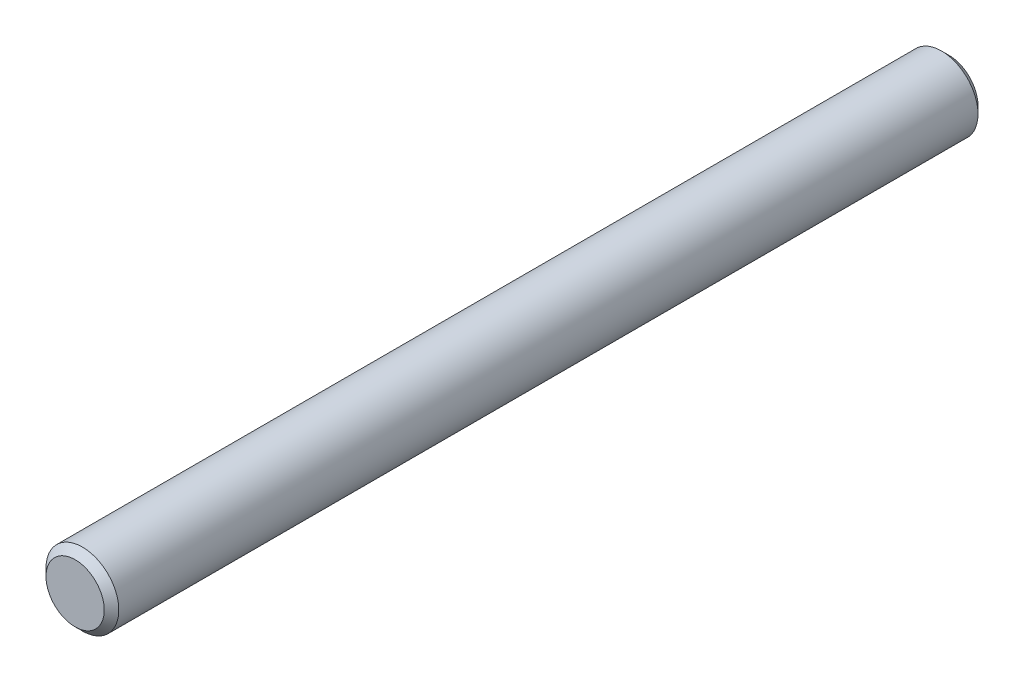
SolidWorks part; units mm, degrees
material "Plain Carbon Steel"
ref_plane "Front" through (0, 0, 0) normal (0, 0, 1) x (1, 0, 0)
ref_plane "Top" through (0, 0, 0) normal (0, 1, 0) x (1, 0, 0)
ref_plane "Right" through (0, 0, 0) normal (1, 0, 0) x (0, 0, -1)
sketch "Sketch1" plane through (0, 0, 0) normal (0, 0, 1) x (1, 0, 0)
  circle A0 centre (0, 0) radius 12.7
  dimension "dia" = 25.4
extrude "Extrude1" add sketch "Sketch1" along normal mid plane 304.8
sketch "Sketch2" plane through (0, 0, 0) normal (1, 0, 0) x (0, 0, -1)
  line L0 (152.4, 12.7) -> (148.59, 12.7) construction
  line L1 (152.4, 12.7) -> (-152.4, 12.7) construction
  line L2 (148.59, 12.7) -> (117.6337, 12.7) construction
  line L3 (117.6337, 12.7) -> (110.49, 12.7) construction
  line L4 (110.49, 12.7) -> (101.6, 12.7) construction
  line L5 (101.6, 12.7) -> (98.9432, 12.7) construction
  line L7 (90.0532, 12.7) -> (83.7032, 12.7) construction
  line L8 (83.7032, 12.7) -> (74.8132, 12.7) construction
  line L10 (-152.4, -12.7) -> (152.4, -12.7) construction
  line L11 (-152.4, 12.7) -> (-149.86, 12.7) construction
  line L12 (-149.86, 12.7) -> (-149.86, -12.7) construction
  line L13 (98.9432, 12.7) -> (90.0532, 12.7) construction
  line L14 (90.0532, 12.7) -> (90.0532, -12.7) construction
  line L15 (110.49, 12.7) -> (110.49, -12.7) construction
  line L16 (74.8132, 12.7) -> (68.4632, 12.7) construction
  line L17 (68.4632, 12.7) -> (59.5732, 12.7) construction
  line L18 (59.5732, 12.7) -> (53.2232, 12.7) construction
  line L19 (53.2232, 12.7) -> (44.3332, 12.7) construction
  line L20 (74.8132, 12.7) -> (74.8132, -12.7) construction
  line L21 (59.5732, 12.7) -> (59.5732, -12.7) construction
  line L22 (44.3332, 12.7) -> (44.3332, -12.7) construction
  line L23 (44.3332, 12.7) -> (37.9832, 12.7) construction
  line L24 (37.9832, 12.7) -> (29.0932, 12.7) construction
  line L25 (29.0932, 12.7) -> (29.0932, -12.7) construction
  line L26 (29.0932, 12.7) -> (22.7432, 12.7) construction
  line L27 (22.7432, 12.7) -> (13.8532, 12.7) construction
  line L28 (13.8532, 12.7) -> (7.5032, 12.7) construction
  line L29 (7.5032, 12.7) -> (-1.3868, 12.7) construction
  line L30 (13.8532, 12.7) -> (13.8532, -12.7) construction
  line L31 (-1.3868, 12.7) -> (-1.3868, -12.7) construction
  line L32 (-1.3868, 12.7) -> (-7.7368, 12.7) construction
  line L33 (-7.7368, 12.7) -> (-16.6268, 12.7) construction
  line L34 (-16.6268, 12.7) -> (-19.2837, 12.7) construction
  line L35 (-19.2837, 12.7) -> (-28.1737, 12.7) construction
  line L36 (-28.1737, 12.7) -> (-28.1737, -12.7) construction
  line L37 (-28.1737, 12.7) -> (-117.0737, 12.7) construction
  line L38 (-117.0737, 12.7) -> (-117.0737, -12.7) construction
  line L39 (101.6, 12.7) -> (101.6, -12.7) construction
  point P0 (-152.4, 12.7)
  point P1 (152.4, 12.7)
  dimension "D1" = 3.81
  dimension "D2" = 30.9562
  dimension "D3" = 7.1437
  dimension "D4" = 8.89
  dimension "D5" = 2.6568
  dimension "D6" = 8.89
  dimension "D7" = 8.89
  dimension "D8" = 2.54
  dimension "D9" = 6.35
  dimension "D10" = 6.35
  dimension "D11" = 8.89
  dimension "D12" = 6.35
  dimension "D13" = 8.89
  dimension "D14" = 6.35
  dimension "D15" = 8.89
  dimension "D16" = 6.35
  dimension "D17" = 8.89
  dimension "D18" = 6.35
  dimension "D19" = 8.89
  dimension "D20" = 6.35
  dimension "D21" = 8.89
  dimension "D22" = 2.6568
  dimension "D23" = 8.89
  dimension "D24" = 88.9
chamfer "Chamfer1" distance 2.54 angle 45 2 edges at (12.7, 0, -152.4) (12.7, 0, 152.4)
sketch "Sketch3" plane through (0, 0, 152.4) normal (0, 0, 1) x (1, 0, 0)
  line L0 (-10.16, 0) -> (10.16, 0) construction
  line L1 (0, 10.16) -> (0, -10.16) construction
  circle A0 centre (0, 0) radius 10.16 construction
  point P7 (0, 0)
equation "\"D1@Chamfer1\" = \"dia@Sketch1\" * .1"
